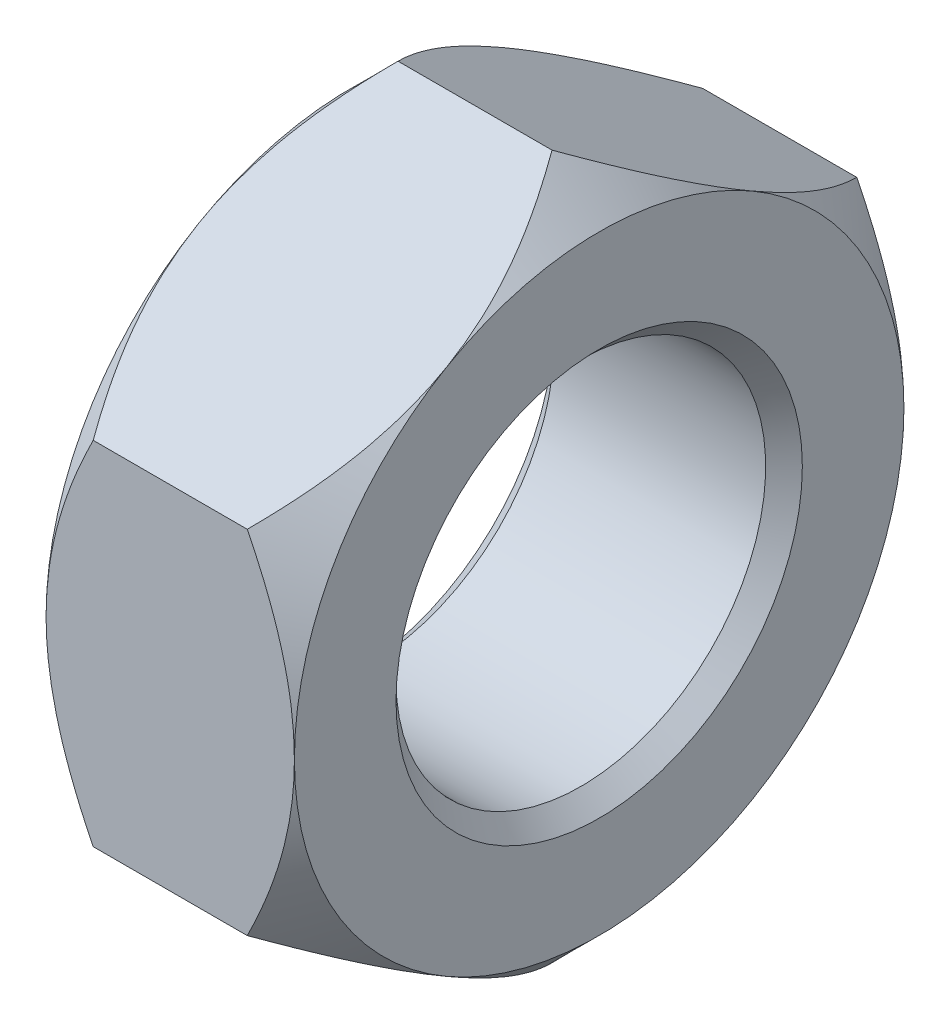
SolidWorks part; units mm, degrees
ref_plane "前视基准面" through (0, 0, 0) normal (0, 0, 1) x (1, 0, 0)
ref_plane "上视基准面" through (0, 0, 0) normal (0, 1, 0) x (1, 0, 0)
ref_plane "右视基准面" through (0, 0, 0) normal (1, 0, 0) x (0, 0, -1)
sketch "草图1" plane through (0, 0, 0) normal (0, 0, 1) x (1, 0, 0)
  line L0 (0, 0) -> (0, 13.5)
  line L1 (0, 13.5) -> (2.7, 16.2)
  line L2 (2.7, 16.2) -> (8.3, 16.2)
  line L3 (8.3, 16.2) -> (11, 13.5)
  line L4 (11, 13.5) -> (11, 0)
  line L5 (11, 0) -> (0, 0)
  line L6 (11, 0) -> (0, 0) construction
revolve "旋转1" add sketch "草图1" angle 360 about L6 reverse direction yes
sketch "草图2" plane through (0, 0, 0) normal (0, 0, 1) x (1, 0, 0)
  line L0 (0, 0) -> (0, 9)
  line L1 (0, 9) -> (0.812, 8.188)
  line L2 (0.812, 8.188) -> (10.188, 8.188)
  line L3 (10.188, 8.188) -> (11, 9)
  line L4 (11, 9) -> (11, 0)
  line L5 (11, 0) -> (0, 0)
  line L6 (11, 0) -> (0, 0) construction
revolve "切除-旋转1" cut sketch "草图2" angle 360 about L6 reverse direction yes
cosmetic thread "装饰螺纹线1" parameters "D1"=11, "D2"=18
sketch "草图3" plane through (0, 0, 0) normal (1, 0, 0) x (0, 0, -1)
  line L0 (-27, 27) -> (-27, -27)
  line L1 (-27, -27) -> (27, -27)
  line L2 (27, -27) -> (27, 27)
  line L3 (27, 27) -> (-27, 27)
  line L4 (-13.5, -7.7942) -> (0, -15.5885)
  line L5 (0, -15.5885) -> (13.5, -7.7942)
  line L6 (13.5, -7.7942) -> (13.5, 7.7942)
  line L7 (13.5, 7.7942) -> (0, 15.5885)
  line L8 (0, 15.5885) -> (-13.5, 7.7942)
  line L9 (-13.5, 7.7942) -> (-13.5, -7.7942)
extrude "切除-拉伸1" cut sketch "草图3" along normal blind 54 and the other way blind 54
ref_plane "基准面1" through (5.5, 0, 0) normal (1, 0, 0) x (0, 0, -1)
ref_plane "nut XY" through (5.5, 0, 0) normal (1, 0, 0) x (0, 0, -1)
ref_plane "nut XZ" through (0, 0, 0) normal (0, -1, 0) x (-1, 0, 0)
ref_plane "nut YZ" through (0, 0, 0) normal (0, 0, -1) x (-1, 0, 0)
ref_axis "nut X" through (5.5, 0, 80.9) along (0, 0, -1)
ref_axis "nut Y" through (5.5, -50, 0) along (0, 1, 0)
ref_axis "nut Z" through (80.9, 0, 0) along (-1, 0, 0)
sketch3d "nut"
  point P0 (5.5, 0, 0)
